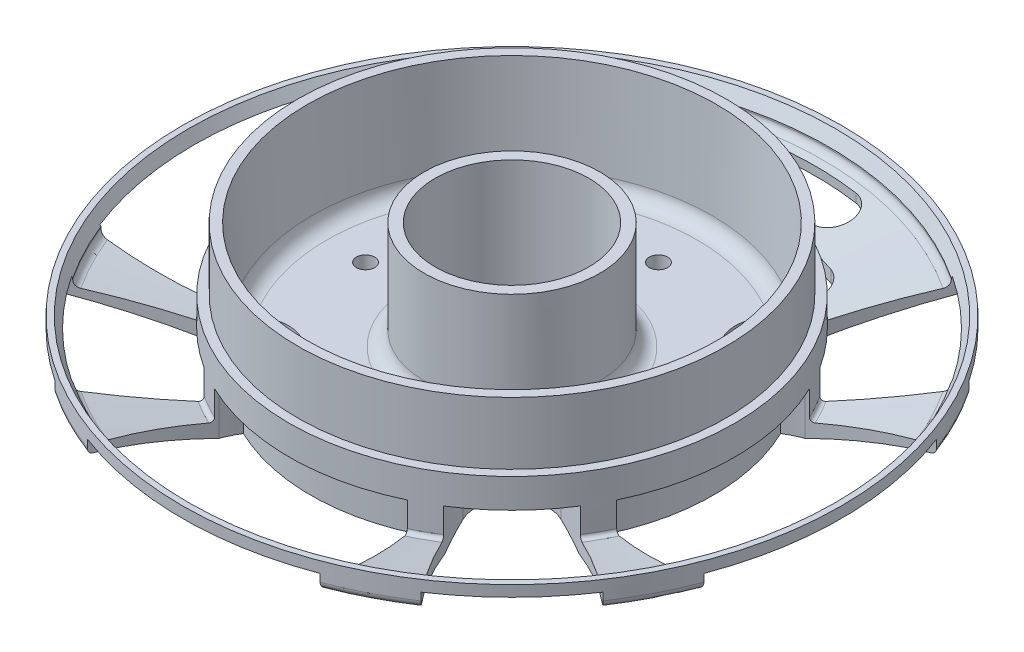
SolidWorks part; units mm, degrees
ref_plane "Front Plane" through (0, 0, 0) normal (0, 0, 1) x (1, 0, 0)
ref_plane "Top Plane" through (0, 0, 0) normal (0, 1, 0) x (1, 0, 0)
ref_plane "Right Plane" through (0, 0, 0) normal (1, 0, 0) x (0, 0, -1)
sketch "Sketch1" plane through (0, 0, 0) normal (0, 0, 1) x (1, 0, 0)
  line L0 (0, 0) -> (0, -26.5) construction
  line L1 (10.5, -26.5) -> (30, -26.5)
  line L2 (30, -26.5) -> (45, -22.3)
  line L3 (45, -22.3) -> (45, -19)
  line L4 (45, -19) -> (44.2, -19)
  line L5 (44.2, -19) -> (43.3, -20.7)
  line L6 (43.3, -21.7) -> (30.45, -24.5)
  line L7 (30.45, -24.5) -> (30.45, -16.5)
  line L8 (30.45, -16.5) -> (29.25, -16.5)
  line L9 (29.25, -16.5) -> (29.25, -8)
  line L10 (29.25, -8) -> (27.95, -8)
  line L11 (27.95, -8) -> (27.2, -22.7)
  line L12 (27.2, -22.7) -> (12, -22.7)
  line L13 (12, -22.7) -> (12, -8)
  line L14 (12, -8) -> (10.5, -8)
  line L15 (10.5, -8) -> (10.5, -26.5)
  line L16 (43.3, -20.7) -> (43.3, -21.7)
  dimension "D1" = 26.5
  dimension "D2" = 45
  dimension "D3" = 10.5
  dimension "D4" = 12
  dimension "D5" = 3.8
  dimension "D6" = 18.5
  dimension "D7" = 27.95
  dimension "D8" = 29.25
  dimension "D9" = 8.5
  dimension "D10" = 1.2
  dimension "D11" = 30
  dimension "D12" = 27.2
  dimension "D13" = 4.2
  dimension "D14" = 3.3
  dimension "D15" = 0.8
  dimension "D16" = 1.7
  dimension "D17" = 1
  dimension "D18" = 2
  dimension "D19" = 2.7
revolve "Revolve1" add sketch "Sketch1" angle 360 about L0
fillet "Fillet1" radius 1 2 edges at (-43.3, -21.7, 0) (-45, -22.3, 0)
fillet "Fillet2" radius 0.5 1 edges at (-30.45, -24.5, 0)
fillet "Fillet3" radius 2 2 edges at (-12, -22.7, 0) (-27.2, -22.7, 0)
sketch "Sketch2" plane through (0, -26.5, 0) normal (0, -1, 0) x (1, 0, 0)
  line L0 (0, 0) -> (0, 45) construction
  line L1 (0, 0) -> (0, -45) construction
  circle A0 centre (0, 0) radius 45 construction
  arc A1 (-13, 27.037) -> (13, 27.037) centre (0, 32.0236) ccw construction
  arc A2 (-15.9, 42.0974) -> (-13, 27.037) centre (27.882, 42.7186) ccw
  circle A3 centre (0, 0) radius 30 construction
  circle A4 centre (0, 0) radius 10.5 construction
  arc A5 (-15.9, 42.0974) -> (15.9, 42.0974) centre (0, 0) cw
  arc A6 (15.9, 42.0974) -> (13, 27.037) centre (-27.882, 42.7186) cw
  arc A7 (27.037, 13) -> (27.037, -13) centre (32.0236, 0) ccw construction
  arc A8 (42.0974, 15.9) -> (27.037, 13) centre (42.7186, -27.882) ccw
  arc A9 (42.0974, 15.9) -> (42.0974, -15.9) centre (0, 0) cw
  arc A10 (42.0974, -15.9) -> (27.037, -13) centre (42.7186, 27.882) cw
  arc A11 (13, -27.037) -> (-13, -27.037) centre (0, -32.0236) ccw construction
  arc A12 (14.2684, -30.8612) -> (13, -27.037) centre (-27.882, -42.7186) ccw
  circle A13 centre (0, 0) radius 45 construction
  arc A14 (-14.2684, -30.8612) -> (-13, -27.037) centre (27.882, -42.7186) cw
  arc A15 (-27.037, -13) -> (-27.037, 13) centre (-32.0236, 0) ccw construction
  arc A16 (-42.0974, -15.9) -> (-27.037, -13) centre (-42.7186, 27.882) ccw
  arc A17 (-42.0974, -15.9) -> (-42.0974, 15.9) centre (0, 0) cw
  arc A18 (-42.0974, 15.9) -> (-27.037, 13) centre (-42.7186, -27.882) cw
  arc A19 (-14.2684, -30.8612) -> (14.2684, -30.8612) centre (0, 0) ccw
  arc A20 (15.9, -42.0974) -> (-15.9, -42.0974) centre (0, 0) cw [skipped]
  arc A21 (5.1097, -35.6355) -> (-5.1097, -35.6355) centre (0, 0) cw
  arc A22 (5.8903, -41.0799) -> (-5.8903, -41.0799) centre (0, 0) cw
  arc A23 (-5.8903, -41.0799) -> (-5.1097, -35.6355) centre (-5.5, -38.3577) cw
  arc A24 (5.8903, -41.0799) -> (5.1097, -35.6355) centre (5.5, -38.3577) ccw
  circle A25 centre (0, 0) radius 27.5 construction
  arc A26 (-24.7926, 11.8987) -> (-24.7926, -11.8987) centre (0, 0) ccw
  arc A27 (-11.8987, -24.7926) -> (11.8987, -24.7926) centre (0, 0) ccw
  arc A28 (24.7926, -11.8987) -> (24.7926, 11.8987) centre (0, 0) ccw
  arc A29 (11.8987, 24.7926) -> (-11.8987, 24.7926) centre (0, 0) ccw
  arc A30 (-13, 27.037) -> (-11.8987, 24.7926) centre (0, 32.0236) ccw
  arc A31 (11.8987, 24.7926) -> (13, 27.037) centre (0, 32.0236) ccw
  arc A32 (-13, -27.037) -> (-11.8987, -24.7926) centre (0, -32.0236) cw
  arc A33 (11.8987, -24.7926) -> (13, -27.037) centre (0, -32.0236) cw
  arc A34 (27.037, -13) -> (24.7926, -11.8987) centre (32.0236, 0) cw
  arc A35 (24.7926, 11.8987) -> (27.037, 13) centre (32.0236, 0) cw
  arc A36 (-27.037, -13) -> (-24.7926, -11.8987) centre (-32.0236, 0) ccw
  arc A37 (-27.037, 13) -> (-24.7926, 11.8987) centre (-32.0236, 0) cw
  point P15 (0, 18.1)
  point P42 (0, 0)
  dimension "D1" = 26
  dimension "D5" = 11
  dimension "D6" = 2
  dimension "D7" = 5.5
  dimension "D9" = 55
  dimension "D2" = 18.1
  dimension "D3" = 31.8
  dimension "D8" = 11
  dimension "D4" = 4
extrude "Cut-Extrude1" cut sketch "Sketch2" against normal blind 6
sketch "Sketch3" plane through (0, -26.5, 0) normal (0, -1, 0) x (1, 0, 0)
  line L0 (0, 0) -> (31.8198, 31.8198) construction
  arc A0 (42.0974, 15.9) -> (15.9, 42.0974) centre (0, 0) ccw construction
  arc A1 (13.2424, 19.9155) -> (19.9155, 13.2424) centre (17.7484, 17.7484) ccw
  arc A2 (24.9829, 37.428) -> (37.428, 24.9829) centre (0, 0) cw
  arc A3 (13.2424, 19.9155) -> (24.9829, 37.428) centre (80.2336, -12.3041) cw
  arc A4 (19.9155, 13.2424) -> (37.428, 24.9829) centre (-12.3041, 80.2336) ccw
  circle A5 centre (0, 0) radius 10.5 construction
  arc A6 (19.9155, -13.2424) -> (13.2424, -19.9155) centre (17.7484, -17.7484) ccw
  arc A7 (37.428, -24.9829) -> (24.9829, -37.428) centre (0, 0) cw
  arc A8 (19.9155, -13.2424) -> (37.428, -24.9829) centre (-12.3041, -80.2336) cw
  arc A9 (13.2424, -19.9155) -> (24.9829, -37.428) centre (80.2336, 12.3041) ccw
  arc A10 (-13.2424, -19.9155) -> (-19.9155, -13.2424) centre (-17.7484, -17.7484) ccw
  arc A11 (-24.9829, -37.428) -> (-37.428, -24.9829) centre (0, 0) cw
  arc A12 (-13.2424, -19.9155) -> (-24.9829, -37.428) centre (-80.2336, 12.3041) cw
  arc A13 (-19.9155, -13.2424) -> (-37.428, -24.9829) centre (12.3041, -80.2336) ccw
  arc A14 (-19.9155, 13.2424) -> (-13.2424, 19.9155) centre (-17.7484, 17.7484) ccw
  arc A15 (-37.428, 24.9829) -> (-24.9829, 37.428) centre (0, 0) cw
  arc A16 (-19.9155, 13.2424) -> (-37.428, 24.9829) centre (12.3041, 80.2336) cw
  arc A17 (-13.2424, 19.9155) -> (-24.9829, 37.428) centre (-80.2336, -12.3041) ccw
  arc A18 (16.1131, 25.3055) -> (25.3055, 16.1131) centre (0, 0) cw construction
  arc A19 (27.037, 13) -> (13, 27.037) centre (0, 0) ccw construction
  point P16 (14.2128, 14.2128)
  point P42 (0, 0)
  point P44 (0, 0)
  dimension "D2" = 5
  dimension "D1" = 17.6
  dimension "D3" = 20.1
  dimension "D4" = 13
  dimension "D5" = 4
extrude "Cut-Extrude2" cut sketch "Sketch3" against normal blind 6
fillet "Fillet4" radius 3 2 edges at (-14.2684, -24.5532, -30.8612) (14.2684, -24.5532, -30.8612)
hole_wizard "Tap Drill for M3x0.5 Tap1" positions "Sketch4" profile "Sketch5" hole size "M3x0.5" standard "ANSI Metric" end condition through all
sketch "Sketch4" plane through (0, -26.5, 0) normal (0, -1, 0) x (-1, 0, 0)
  point P0 (0, 20)
  point P6 (20, 0)
  point P7 (0, -20)
  point P8 (-20, 0)
  dimension "D2" = 20
  dimension "D1" = 4
sketch "Sketch5" plane through (0, -26.5, -20) normal (1, 0, 0) x (0, 0, -1)
  line L0 (0, 0) -> (0, 18.5)
  line L1 (0, 18.5) -> (1.25, 18.5)
  line L2 (1.25, 18.5) -> (1.25, 0)
  line L5 (1.25, 0) -> (0, 0)
  line L11 (0, -6.35) -> (0, 107.95) construction
  dimension "Thru Hole Dia." = 2.5
  dimension "Thru Hole Depth" = 18.5
